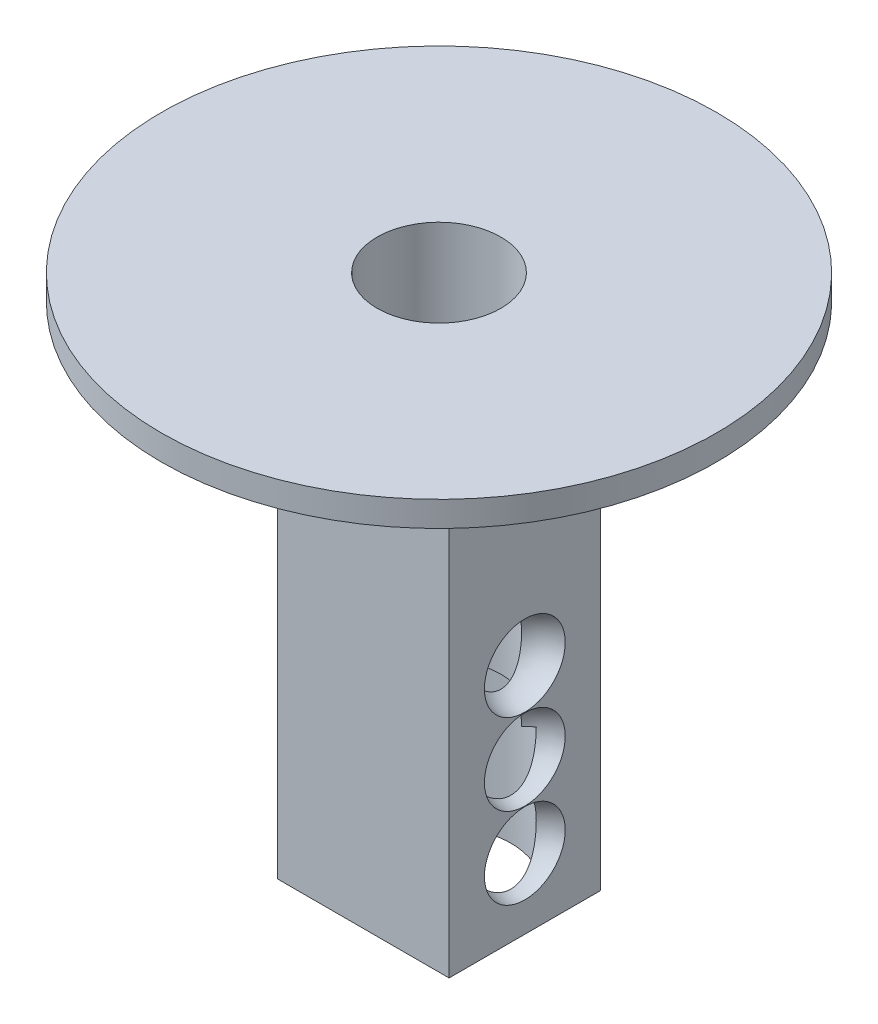
SolidWorks part; units mm, degrees
ref_plane "前视基准面" through (0, 0, 0) normal (0, 0, 1) x (1, 0, 0)
ref_plane "上视基准面" through (0, 0, 0) normal (0, 1, 0) x (1, 0, 0)
ref_plane "右视基准面" through (0, 0, 0) normal (1, 0, 0) x (0, 0, -1)
other "Configuration Table"
sketch "草图5" plane through (0, 0, 0) normal (0, 0, 1) x (1, 0, 0)
  line L1 (-17, 70) -> (0, 70)
  line L2 (-17, 70) -> (-17, -30)
  line L3 (-17, -30) -> (0, -30)
  line L4 (0, 70) -> (0, -30)
  dimension "D1" = 100
  dimension "D2" = 30
  dimension "D3" = 17
extrude "凸台-拉伸1" add sketch "草图5" along normal blind 15 and the other way blind 15
sketch "草图7" plane through (0, 0, 0) normal (0, 0, 1) x (1, 0, 0)
  line L0 (-17, -30) -> (0, -30) construction
  line L2 (-17, 70) -> (-17, -30) construction
  line L4 (-17, 8) -> (-17, -8)
  arc A1 (-17, -8) -> (-17, 8) centre (-17, 0) ccw
  dimension "D1" = 0
  dimension "D2" = 8
  dimension "D3" = 30
revolve "切除-旋转1" cut sketch "草图7" angle 360 about L4
pattern_linear "阵列(线性)1" count 2 spacing 16.1 along (0, 1, 0) count 2 spacing 16.1 along (0, -1, 0) of "切除-旋转1" pattern seed only yes
mirror "镜向2" about plane through (0, 0, 0) normal (1, 0, 0) of "凸台-拉伸1"
mirror "镜向3" about plane through (0, 0, 0) normal (1, 0, 0) of "切除-旋转1"
mirror "镜向4" about plane through (0, 0, 0) normal (1, 0, 0) of "阵列(线性)1"
sketch "草图9" plane through (0, 0, 0) normal (0, 0, 1) x (1, 0, 0)
  line L0 (17, 70) -> (-17, 70) construction
  line L1 (0, 70) -> (55, 70)
  line L2 (0, 70) -> (0, 75)
  line L3 (0, 75) -> (55, 75)
  line L4 (55, 70) -> (55, 75)
  dimension "D1" = 55
  dimension "D2" = 5
revolve "旋转1" add sketch "草图9" angle 360 about L2
sketch "草图12" plane through (0, 0, 0) normal (0, 1, 0) x (1, 0, 0)
  circle A0 centre (0, 0) radius 12.25
  dimension "D1" = 24.5
extrude "切除-拉伸1" cut sketch "草图12" against normal through all and the other way through all
sketch "草图15" plane through (0, 0, 0) normal (0, 1, 0) x (1, 0, 0)
  circle A0 centre (0, 0) radius 14.25
  dimension "D1" = 28.5
extrude "切除-拉伸4" cut sketch "草图15" against normal through all
